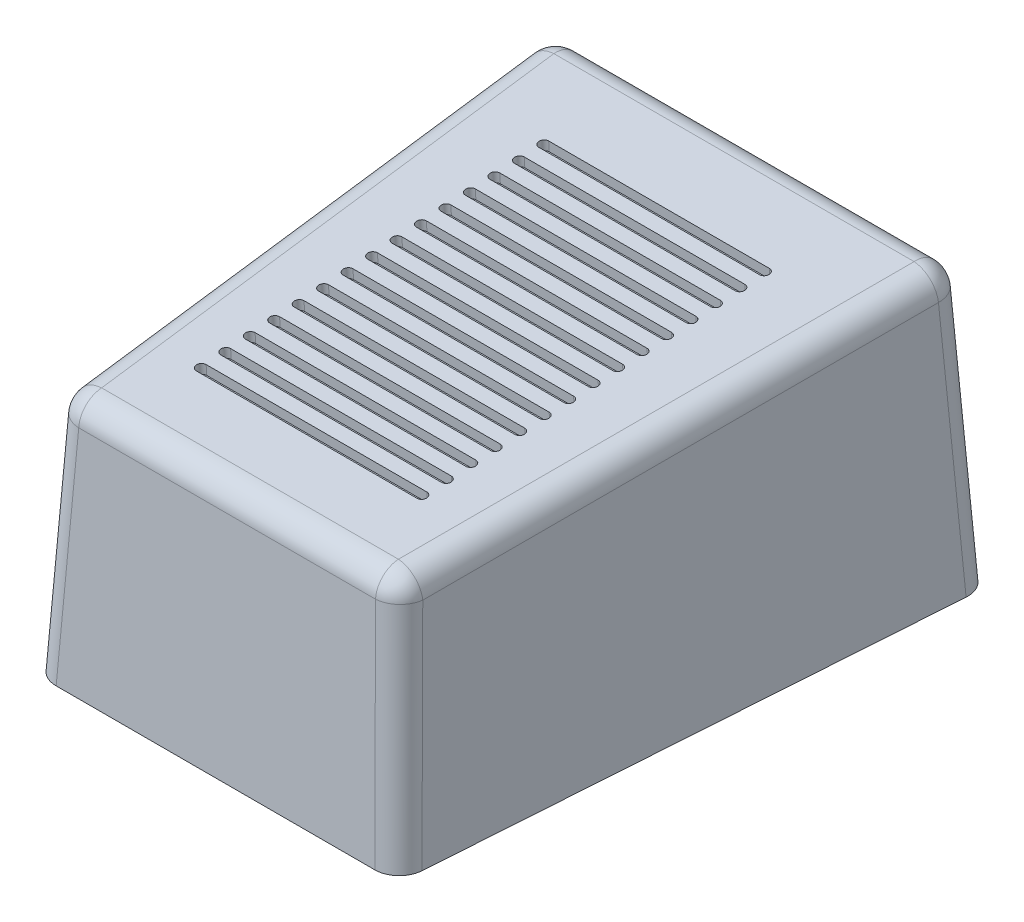
SolidWorks part; units mm, degrees
material "ABS"
ref_plane "Front Plane" through (0, 0, 0) normal (0, 0, 1) x (1, 0, 0)
ref_plane "Top Plane" through (0, 0, 0) normal (0, 1, 0) x (1, 0, 0)
ref_plane "Right Plane" through (0, 0, 0) normal (1, 0, 0) x (0, 0, -1)
sketch "Sketch1" plane through (0, 0, 0) normal (0, 1, 0) x (1, 0, 0)
  line L0 (0, 0) -> (74.3, 0)
  line L4 (0, 0) -> (-7.85, 113.7899)
  line L5 (-7.85, 113.7899) -> (82.15, 113.7899)
  line L6 (82.15, 113.7899) -> (74.3, 0)
  dimension "D1" = 90
  dimension "D2" = 74.3
extrude "Boss-Extrude1" add sketch "Sketch1" along normal blind 57 draft 3 contours L4 L5 L6 L0
sketch "Sketch3" plane through (0, 0, 0) normal (-0.9963, 0.0523, 0.0687) x (0.0686, -0.0036, 0.9976)
  line L0 (-111.0653, 56.6776) -> (-2.9943, 57.0678)
  line L1 (-2.9943, 57.0678) -> (-2.623, 49.9909)
  line L2 (-2.9943, 57.0678) -> (0, 0) construction
  line L3 (-2.623, 49.9909) -> (-111.0653, 56.6776)
  line L4 (0, 0) -> (-114.0596, -0.4118) construction
  dimension "D1" = 50
extrude "Cut-Extrude5" cut sketch "Sketch3" along direction (-1, 0, 0) on the side against the normal through all
fillet "Fillet1" radius 5 8 edges at (37.15, 49.9315, -2.6168) (-1.1035, 53.4657, -56.7097) (37.15, 57, -110.8027) (75.4035, 53.4657, -56.7097) (80.5498, 28.5, -112.2963) (-6.2498, 28.5, -112.2963) (73.0788, 24.9657, -1.3084) (1.2212, 24.9657, -1.3084)
sketch "Sketch4" plane through (0, 49.549, 3.2374) normal (0, 0.9979, 0.0652) x (1, 0, 0)
  line L0 (14.3292, 93.21) -> (59.3292, 93.21) construction
  line L1 (14.3292, 94.21) -> (59.3292, 94.21)
  line L2 (14.3292, 92.21) -> (59.3292, 92.21)
  line L3 (14.3292, 88.21) -> (59.3292, 88.21) construction
  line L4 (14.3292, 89.21) -> (59.3292, 89.21)
  line L5 (14.3292, 87.21) -> (59.3292, 87.21)
  line L6 (14.3292, 83.21) -> (59.3292, 83.21) construction
  line L7 (14.3292, 84.21) -> (59.3292, 84.21)
  line L8 (14.3292, 82.21) -> (59.3292, 82.21)
  line L9 (14.3292, 78.21) -> (59.3292, 78.21) construction
  line L10 (14.3292, 79.21) -> (59.3292, 79.21)
  line L11 (14.3292, 77.21) -> (59.3292, 77.21)
  line L12 (14.3292, 73.21) -> (59.3292, 73.21) construction
  line L13 (14.3292, 74.21) -> (59.3292, 74.21)
  line L14 (14.3292, 72.21) -> (59.3292, 72.21)
  line L15 (14.3292, 68.21) -> (59.3292, 68.21) construction
  line L16 (14.3292, 69.21) -> (59.3292, 69.21)
  line L17 (14.3292, 67.21) -> (59.3292, 67.21)
  line L18 (14.3292, 63.21) -> (59.3292, 63.21) construction
  line L19 (14.3292, 64.21) -> (59.3292, 64.21)
  line L20 (14.3292, 62.21) -> (59.3292, 62.21)
  line L21 (14.3292, 58.21) -> (59.3292, 58.21) construction
  line L22 (14.3292, 59.21) -> (59.3292, 59.21)
  line L23 (14.3292, 57.21) -> (59.3292, 57.21)
  line L24 (14.3292, 53.21) -> (59.3292, 53.21) construction
  line L25 (14.3292, 54.21) -> (59.3292, 54.21)
  line L26 (14.3292, 52.21) -> (59.3292, 52.21)
  line L27 (14.3292, 48.21) -> (59.3292, 48.21) construction
  line L28 (14.3292, 49.21) -> (59.3292, 49.21)
  line L29 (14.3292, 47.21) -> (59.3292, 47.21)
  line L30 (14.3292, 43.21) -> (59.3292, 43.21) construction
  line L31 (14.3292, 44.21) -> (59.3292, 44.21)
  line L32 (14.3292, 42.21) -> (59.3292, 42.21)
  line L33 (14.3292, 38.21) -> (59.3292, 38.21) construction
  line L34 (14.3292, 39.21) -> (59.3292, 39.21)
  line L35 (14.3292, 37.21) -> (59.3292, 37.21)
  line L36 (14.3292, 33.21) -> (59.3292, 33.21) construction
  line L37 (14.3292, 34.21) -> (59.3292, 34.21)
  line L38 (14.3292, 32.21) -> (59.3292, 32.21)
  line L39 (14.3292, 28.21) -> (59.3292, 28.21) construction
  line L40 (14.3292, 29.21) -> (59.3292, 29.21)
  line L41 (14.3292, 27.21) -> (59.3292, 27.21)
  line L42 (14.3292, 23.21) -> (59.3292, 23.21) construction
  line L43 (14.3292, 24.21) -> (59.3292, 24.21)
  line L44 (14.3292, 22.21) -> (59.3292, 22.21)
  arc A0 (14.3292, 94.21) -> (14.3292, 92.21) centre (14.3292, 93.21) ccw
  arc A1 (59.3292, 92.21) -> (59.3292, 94.21) centre (59.3292, 93.21) ccw
  arc A2 (14.3292, 89.21) -> (14.3292, 87.21) centre (14.3292, 88.21) ccw
  arc A3 (59.3292, 87.21) -> (59.3292, 89.21) centre (59.3292, 88.21) ccw
  arc A4 (14.3292, 84.21) -> (14.3292, 82.21) centre (14.3292, 83.21) ccw
  arc A5 (59.3292, 82.21) -> (59.3292, 84.21) centre (59.3292, 83.21) ccw
  arc A6 (14.3292, 79.21) -> (14.3292, 77.21) centre (14.3292, 78.21) ccw
  arc A7 (59.3292, 77.21) -> (59.3292, 79.21) centre (59.3292, 78.21) ccw
  arc A8 (14.3292, 74.21) -> (14.3292, 72.21) centre (14.3292, 73.21) ccw
  arc A9 (59.3292, 72.21) -> (59.3292, 74.21) centre (59.3292, 73.21) ccw
  arc A10 (14.3292, 69.21) -> (14.3292, 67.21) centre (14.3292, 68.21) ccw
  arc A11 (59.3292, 67.21) -> (59.3292, 69.21) centre (59.3292, 68.21) ccw
  arc A12 (14.3292, 64.21) -> (14.3292, 62.21) centre (14.3292, 63.21) ccw
  arc A13 (59.3292, 62.21) -> (59.3292, 64.21) centre (59.3292, 63.21) ccw
  arc A14 (14.3292, 59.21) -> (14.3292, 57.21) centre (14.3292, 58.21) ccw
  arc A15 (59.3292, 57.21) -> (59.3292, 59.21) centre (59.3292, 58.21) ccw
  arc A16 (14.3292, 54.21) -> (14.3292, 52.21) centre (14.3292, 53.21) ccw
  arc A17 (59.3292, 52.21) -> (59.3292, 54.21) centre (59.3292, 53.21) ccw
  arc A18 (14.3292, 49.21) -> (14.3292, 47.21) centre (14.3292, 48.21) ccw
  arc A19 (59.3292, 47.21) -> (59.3292, 49.21) centre (59.3292, 48.21) ccw
  arc A20 (14.3292, 44.21) -> (14.3292, 42.21) centre (14.3292, 43.21) ccw
  arc A21 (59.3292, 42.21) -> (59.3292, 44.21) centre (59.3292, 43.21) ccw
  arc A22 (14.3292, 39.21) -> (14.3292, 37.21) centre (14.3292, 38.21) ccw
  arc A23 (59.3292, 37.21) -> (59.3292, 39.21) centre (59.3292, 38.21) ccw
  arc A24 (14.3292, 34.21) -> (14.3292, 32.21) centre (14.3292, 33.21) ccw
  arc A25 (59.3292, 32.21) -> (59.3292, 34.21) centre (59.3292, 33.21) ccw
  arc A26 (14.3292, 29.21) -> (14.3292, 27.21) centre (14.3292, 28.21) ccw
  arc A27 (59.3292, 27.21) -> (59.3292, 29.21) centre (59.3292, 28.21) ccw
  arc A28 (14.3292, 24.21) -> (14.3292, 22.21) centre (14.3292, 23.21) ccw
  arc A29 (59.3292, 22.21) -> (59.3292, 24.21) centre (59.3292, 23.21) ccw
  point P2 (36.8292, 93.21)
  point P11 (36.8292, 88.21)
  point P18 (36.8292, 83.21)
  point P25 (36.8292, 78.21)
  point P32 (36.8292, 73.21)
  point P39 (36.8292, 68.21)
  point P46 (36.8292, 63.21)
  point P53 (36.8292, 58.21)
  point P60 (36.8292, 53.21)
  point P67 (36.8292, 48.21)
  point P74 (36.8292, 43.21)
  point P81 (36.8292, 38.21)
  point P88 (36.8292, 33.21)
  point P95 (36.8292, 28.21)
  point P102 (36.8292, 23.21)
  dimension "D1" = 2
  dimension "D2" = 45
  dimension "D3" = 37.15
  dimension "D4" = 15
extrude "Cut-Extrude6" cut sketch "Sketch4" against normal blind 2
